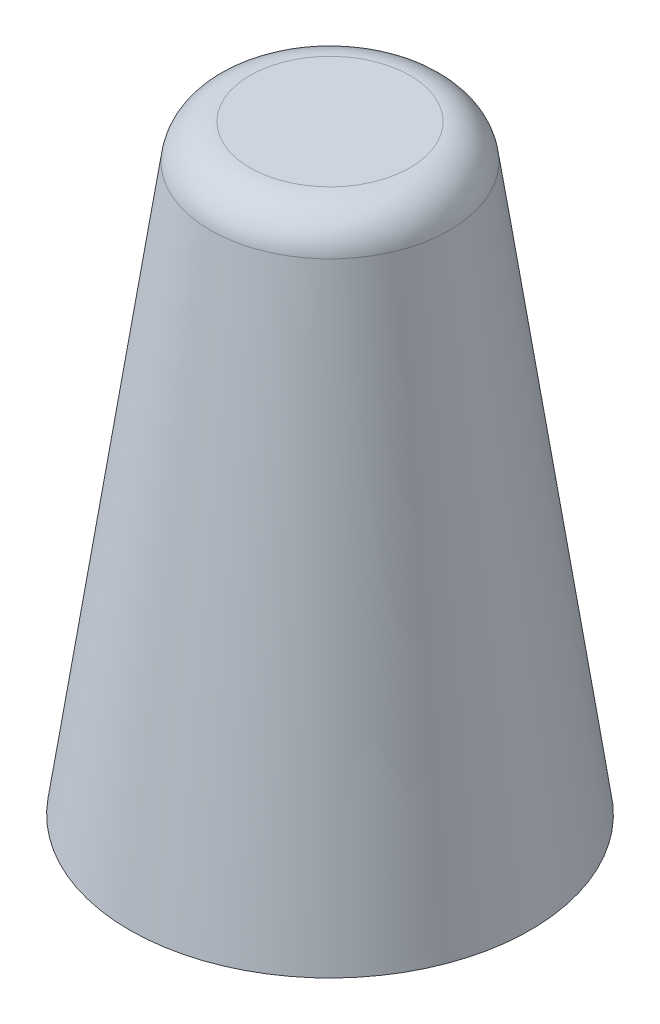
SolidWorks part; units mm, degrees
ref_plane "Front Plane" through (0, 0, 0) normal (0, 0, 1) x (1, 0, 0)
ref_plane "Top Plane" through (0, 0, 0) normal (0, 1, 0) x (1, 0, 0)
ref_plane "Right Plane" through (0, 0, 0) normal (1, 0, 0) x (0, 0, -1)
sketch "Sketch2" plane through (0, 0, 0) normal (0, 1, 0) x (1, 0, 0)
  circle A0 centre (0, 0) radius 0.65
  circle A1 centre (0, 0) radius 1.65
  dimension "D1" = 1.3
  dimension "D2" = 1
extrude "Boss-Extrude1" add sketch "Sketch2" along normal blind 14
sketch "Sketch4" plane through (0, 0, 0) normal (0, 0, 1) x (1, 0, 0)
  line L0 (0, 0) -> (4, 0)
  line L1 (0, 0) -> (0, 14)
  line L2 (4, 0) -> (2, 14)
  line L3 (5.0102, 0) -> (3.0102, 14)
  line L4 (3.0102, 14) -> (0, 14)
  line L5 (0, 14) -> (0, 15)
  line L6 (0, 15) -> (2.8673, 15)
  line L7 (2.8673, 15) -> (3.0102, 14)
  line L8 (4, 0) -> (5.0102, 0)
  dimension "D1" = 14
  dimension "D2" = 4
  dimension "2" = 2
  dimension "D4" = 1
  dimension "D5" = 1
revolve "Revolve1" add sketch "Sketch4" angle 360 about L1
chamfer "Chamfer1" distance 5 angle 45 1 edges at (0, 14, 1.65)
fillet "Fillet1" radius 1 1 edges at (0, 15, -2.8673)
